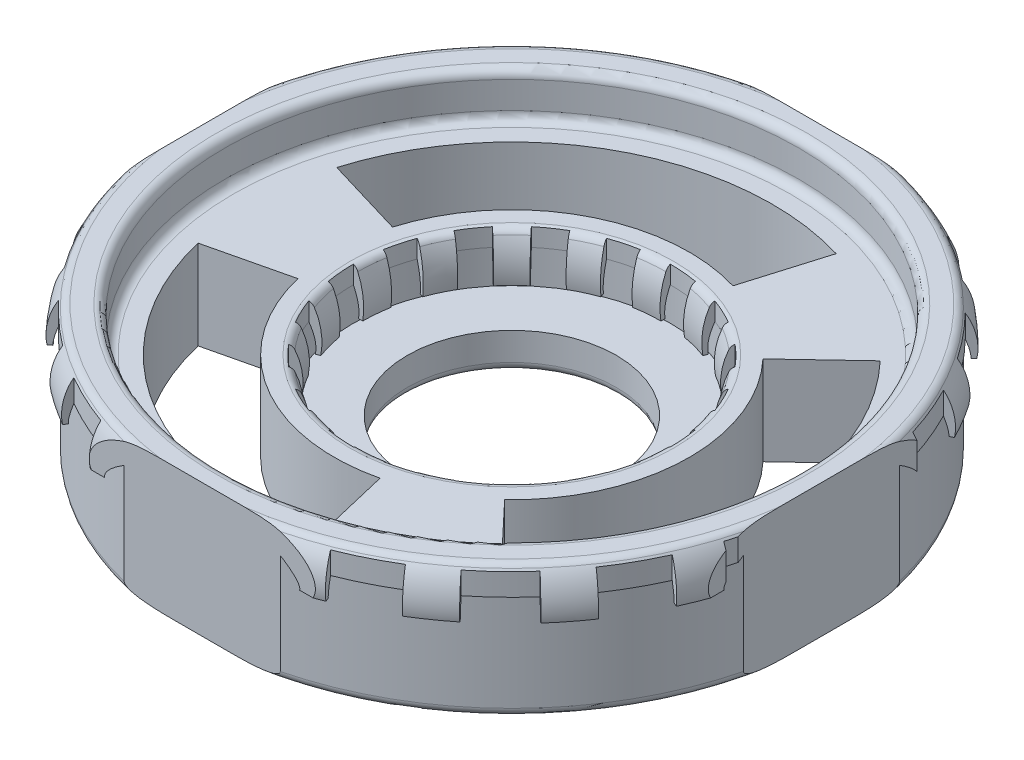
SolidWorks part; units mm, degrees
ref_plane "Front Plane" through (0, 0, 0) normal (0, 0, 1) x (1, 0, 0)
ref_plane "Top Plane" through (0, 0, 0) normal (0, 1, 0) x (1, 0, 0)
ref_plane "Right Plane" through (0, 0, 0) normal (1, 0, 0) x (0, 0, -1)
sketch "Sketch1" plane through (0, 0, 0) normal (0, 0, 1) x (1, 0, 0)
  line L0 (0, 0) -> (0, 51.2475) construction
  line L1 (34.9, 0.0906) -> (34.9, 51.2475) construction
  line L2 (77, 51.2475) -> (77, 0) construction
  line L3 (37.9014, 10.7092) -> (65.2004, 10.7092)
  line L4 (24.4669, -1.6378) -> (24.4669, -8.1437)
  line L5 (26.4669, -10.1437) -> (72.7675, -10.1437)
  line L6 (74.7675, -8.1437) -> (74.7675, 15.3893)
  line L7 (77, 10.6185) -> (76, 10.6185)
  line L8 (67.2004, 12.7092) -> (67.2004, 19.0341)
  line L9 (69.2004, 21.0341) -> (73.1718, 21.0341)
  line L10 (34.9, 0.0906) -> (35.9, 0.0906)
  line L11 (37.2844, 6.7204) -> (37.2844, -1.6378)
  line L12 (37.2844, -1.6378) -> (24.4669, -1.6378)
  line L13 (34.6953, 0.2119) -> (34.6953, 7.6549) construction
  arc A0 (65.2004, 10.7092) -> (67.2004, 12.7092) centre (65.2004, 12.7092) ccw
  arc A1 (73.1718, 21.0341) -> (74.7675, 20.2398) centre (73.1718, 19.0341) cw
  arc A2 (69.2004, 21.0341) -> (67.2004, 19.0341) centre (69.2004, 19.0341) ccw
  arc A3 (36.0692, 9.511) -> (37.9014, 10.7092) centre (37.9014, 8.7092) cw
  arc A4 (72.7675, -10.1437) -> (74.7675, -8.1437) centre (72.7675, -8.1437) ccw
  arc A5 (24.4669, -8.1437) -> (26.4669, -10.1437) centre (26.4669, -8.1437) ccw
  spline S0 degree 3 poles (74.7675, 20.2398) (76.6978, 17.6849) (77.6185, 13.7523) (77, 10.6185) knots 0.096278 0.096278 0.096278 0.096278 1 1 1 1
  spline S1 degree 2 poles (76, 10.6185) (76.1632, 11.9442) (74.7675, 15.3893) knots 0 0 0 1 1 1
  spline S2 degree 3 poles (34.9, 0.0906) (34.41, 3.4699) (34.7997, 6.61) (36.0692, 9.511) knots 0 0 0 0 0.87775 0.87775 0.87775 0.87775
  spline S3 degree 2 poles (35.9, 0.0906) (35.3744, 2.9003) (37.2844, 6.7204) knots 0 0 0 1 1 1
  dimension "D4" = 2
  dimension "D6" = 2
  dimension "D1" = 34.9
  dimension "D2" = 77
  dimension "D3" = 1
  dimension "D5" = 1
  dimension "D7" = 0.2047
revolve "Revolve1" add sketch "Sketch1" angle 360 about L0
sketch "Sketch2" plane through (0, 10.7092, 0) normal (0, 1, 0) x (1, 0, 0)
  line L0 (0, 0) -> (76.2471, 71.9973) construction
  line L1 (28.5597, -30.2455) -> (41.8961, -44.3692)
  line L2 (30.2455, 28.5597) -> (44.3692, 41.8961)
  arc A0 (44.3692, 41.8961) -> (41.8961, -44.3692) centre (0, 0) cw
  arc A1 (28.5597, -30.2455) -> (30.2455, 28.5597) centre (0, 0) ccw
extrude "Cut-Extrude1" cut sketch "Sketch2" against normal through all
ref_axis "Axis1" through (0, 22.593, 0) along (0, -1, 0)
pattern_circular "CirPattern1" count 3 over 360 about axis through (0, 22.593, 0) along (0, -1, 0) of "Cut-Extrude1"
sketch "Sketch3" plane through (0, 10.7092, 0) normal (0, 1, 0) x (1, 0, 0)
  line L0 (0, 0) -> (101.7787, 17.9463) construction
  line L1 (0, 0) -> (103.9254, 0) construction
  line L2 (33.5649, 5.9184) -> (36.5364, 6.4423)
  line L3 (34.0827, 0) -> (37.1, 0)
  arc A0 (37.1, 0) -> (36.5364, 6.4423) centre (0, 0) ccw
  arc A1 (34.0827, 0) -> (33.5649, 5.9184) centre (0, 0) ccw
extrude "Cut-Extrude2" cut sketch "Sketch3" against normal blind 12
pattern_circular "CirPattern2" count 18 over 360 about axis through (0, 22.593, 0) along (0, -1, 0) of "Cut-Extrude2"
sketch "Sketch4" plane through (0, 21.0341, 0) normal (0, 1, 0) x (1, 0, 0)
  line L0 (0, 0) -> (89.5731, 15.7941) construction
  line L1 (0, 0) -> (100.3555, 0) construction
  line L2 (73.9381, 13.0373) -> (78.1272, 13.7759)
  line L3 (75.0787, 0) -> (79.3324, 0)
  arc A0 (79.3324, 0) -> (78.1272, 13.7759) centre (0, 0) ccw
  arc A1 (75.0787, 0) -> (73.9381, 13.0373) centre (0, 0) ccw
extrude "Cut-Extrude3" cut sketch "Sketch4" against normal blind 12
pattern_circular "CirPattern3" count 21 over 360 about axis through (0, 22.593, 0) along (0, -1, 0) of "Cut-Extrude3"
sketch "Sketch5" plane through (0, 0, 0) normal (0, 1, 0) x (1, 0, 0)
  line L1 (-72.5, -72.5) -> (72.5, -72.5)
  line L2 (-72.5, -72.5) -> (-72.5, 72.5)
  line L3 (-72.5, 72.5) -> (72.5, 72.5)
  line L4 (72.5, -72.5) -> (72.5, 72.5)
  line L5 (-72.5, -72.5) -> (72.5, 72.5) construction
  line L6 (-72.5, 72.5) -> (72.5, -72.5) construction
  line L7 (-98.3121, 84.0615) -> (92.7744, 84.0615)
  line L8 (-98.3121, 84.0615) -> (-98.3121, -85.9697)
  line L9 (-98.3121, -85.9697) -> (92.7744, -85.9697)
  line L10 (92.7744, 84.0615) -> (92.7744, -85.9697)
  point P0 (0, 0)
extrude "Cut-Extrude4" cut sketch "Sketch5" against normal through all and the other way through all
